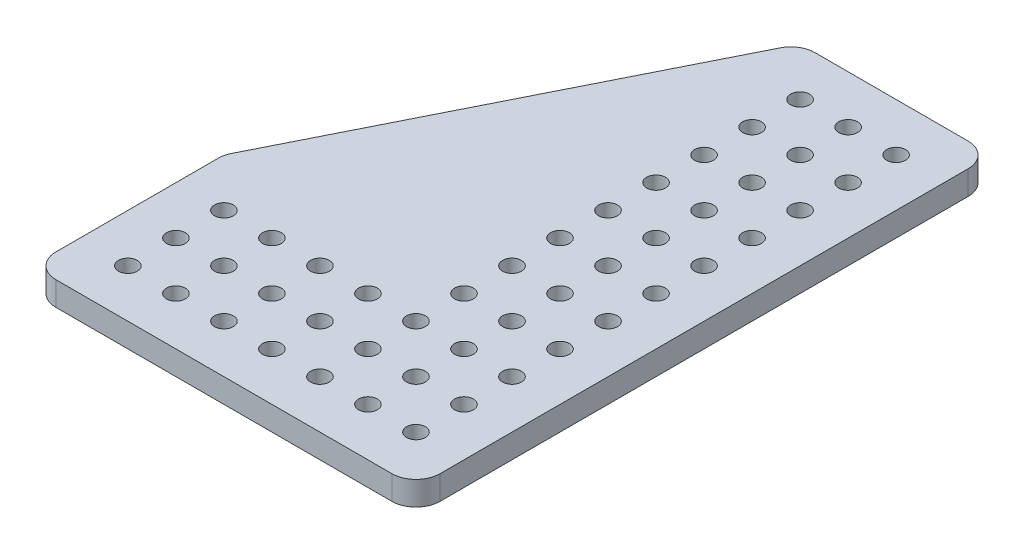
SolidWorks part; units mm, degrees
material "6061-T6 (SS)"
ref_plane "Front Plane" through (0, 0, 0) normal (0, 0, 1) x (1, 0, 0)
ref_plane "Top Plane" through (0, 0, 0) normal (0, 1, 0) x (1, 0, 0)
ref_plane "Right Plane" through (0, 0, 0) normal (1, 0, 0) x (0, 0, -1)
sketch "Sketch1" plane through (0, 0, 0) normal (0, 1, 0) x (1, 0, 0)
  line L0 (0, 50.8) -> (50.8, 152.4)
  line L1 (0, 0) -> (101.6, 0)
  line L2 (0, 0) -> (0, 50.8)
  line L3 (50.8, 152.4) -> (101.6, 152.4)
  line L4 (101.6, 0) -> (101.6, 152.4)
  dimension "D1" = 101.6
  dimension "D2" = 152.4
  dimension "D3" = 50.8
  dimension "D4" = 50.8
extrude "Boss-Extrude1" add sketch "Sketch1" along normal blind 6.35
sketch "Sketch2" plane through (0, 6.35, 0) normal (0, 1, 0) x (1, 0, 0)
  line L0 (0, 0) -> (101.6, 0) construction
  line L1 (101.6, 0) -> (101.6, 152.4) construction
  circle A0 centre (88.9, 12.7) radius 2.4892
  circle A1 centre (76.2, 12.7) radius 2.4892
  circle A2 centre (63.5, 12.7) radius 2.4892
  circle A3 centre (50.8, 12.7) radius 2.4892
  circle A4 centre (38.1, 12.7) radius 2.4892
  circle A5 centre (25.4, 12.7) radius 2.4892
  circle A6 centre (12.7, 12.7) radius 2.4892
  circle A7 centre (76.2, 25.4) radius 2.4892
  circle A8 centre (63.5, 25.4) radius 2.4892
  circle A9 centre (50.8, 25.4) radius 2.4892
  circle A10 centre (38.1, 25.4) radius 2.4892
  circle A11 centre (25.4, 25.4) radius 2.4892
  circle A12 centre (12.7, 25.4) radius 2.4892
  circle A13 centre (76.2, 38.1) radius 2.4892
  circle A14 centre (63.5, 38.1) radius 2.4892
  circle A15 centre (50.8, 38.1) radius 2.4892
  circle A16 centre (38.1, 38.1) radius 2.4892
  circle A17 centre (25.4, 38.1) radius 2.4892
  circle A18 centre (12.7, 38.1) radius 2.4892
  circle A19 centre (76.2, 50.8) radius 2.4892
  circle A20 centre (63.5, 50.8) radius 2.4892
  circle A21 centre (50.8, 50.8) radius 2.4892 construction
  circle A22 centre (38.1, 50.8) radius 2.4892 construction
  circle A23 centre (25.4, 50.8) radius 2.4892 construction
  circle A24 centre (12.7, 50.8) radius 2.4892 construction
  circle A25 centre (76.2, 63.5) radius 2.4892
  circle A26 centre (63.5, 63.5) radius 2.4892
  circle A27 centre (50.8, 63.5) radius 2.4892 construction
  circle A28 centre (38.1, 63.5) radius 2.4892 construction
  circle A29 centre (25.4, 63.5) radius 2.4892 construction
  circle A30 centre (12.7, 63.5) radius 2.4892 construction
  circle A31 centre (76.2, 76.2) radius 2.4892
  circle A32 centre (63.5, 76.2) radius 2.4892
  circle A33 centre (50.8, 76.2) radius 2.4892 construction
  circle A34 centre (38.1, 76.2) radius 2.4892 construction
  circle A35 centre (25.4, 76.2) radius 2.4892 construction
  circle A36 centre (12.7, 76.2) radius 2.4892 construction
  circle A37 centre (76.2, 88.9) radius 2.4892
  circle A38 centre (63.5, 88.9) radius 2.4892
  circle A39 centre (50.8, 88.9) radius 2.4892 construction
  circle A40 centre (38.1, 88.9) radius 2.4892 construction
  circle A41 centre (25.4, 88.9) radius 2.4892 construction
  circle A42 centre (12.7, 88.9) radius 2.4892 construction
  circle A43 centre (76.2, 101.6) radius 2.4892
  circle A44 centre (63.5, 101.6) radius 2.4892
  circle A45 centre (50.8, 101.6) radius 2.4892 construction
  circle A46 centre (38.1, 101.6) radius 2.4892 construction
  circle A47 centre (25.4, 101.6) radius 2.4892 construction
  circle A48 centre (12.7, 101.6) radius 2.4892 construction
  circle A49 centre (76.2, 114.3) radius 2.4892
  circle A50 centre (63.5, 114.3) radius 2.4892
  circle A51 centre (50.8, 114.3) radius 2.4892 construction
  circle A52 centre (38.1, 114.3) radius 2.4892 construction
  circle A53 centre (25.4, 114.3) radius 2.4892 construction
  circle A54 centre (12.7, 114.3) radius 2.4892 construction
  circle A55 centre (76.2, 127) radius 2.4892
  circle A56 centre (63.5, 127) radius 2.4892
  circle A57 centre (50.8, 127) radius 2.4892 construction
  circle A58 centre (38.1, 127) radius 2.4892 construction
  circle A59 centre (25.4, 127) radius 2.4892 construction
  circle A60 centre (12.7, 127) radius 2.4892 construction
  circle A61 centre (76.2, 139.7) radius 2.4892
  circle A62 centre (63.5, 139.7) radius 2.4892
  circle A63 centre (50.8, 139.7) radius 2.4892 construction
  circle A64 centre (38.1, 139.7) radius 2.4892 construction
  circle A65 centre (25.4, 139.7) radius 2.4892 construction
  circle A66 centre (12.7, 139.7) radius 2.4892 construction
  circle A67 centre (88.9, 25.4) radius 2.4892
  circle A68 centre (88.9, 38.1) radius 2.4892
  circle A69 centre (88.9, 50.8) radius 2.4892
  circle A70 centre (88.9, 63.5) radius 2.4892
  circle A71 centre (88.9, 76.2) radius 2.4892
  circle A72 centre (88.9, 88.9) radius 2.4892
  circle A73 centre (88.9, 101.6) radius 2.4892
  circle A74 centre (88.9, 114.3) radius 2.4892
  circle A75 centre (88.9, 127) radius 2.4892
  circle A76 centre (88.9, 139.7) radius 2.4892
  point P7 (0, 0)
  dimension "D2" = 12.7
  dimension "D3" = 4.9784
  dimension "D6" = 12.7
  dimension "D7" = 12.7
  dimension "D1" = 12.7
  dimension "D5" = 7
  dimension "D4" = 11
extrude "Cut-Extrude1" cut sketch "Sketch2" against normal through all
fillet "Fillet1" radius 6.35 5 edges at (0, 3.175, -50.8) (101.6, 3.175, -152.4) (101.6, 3.175, 0) (0, 3.175, 0) (50.8, 3.175, -152.4)
